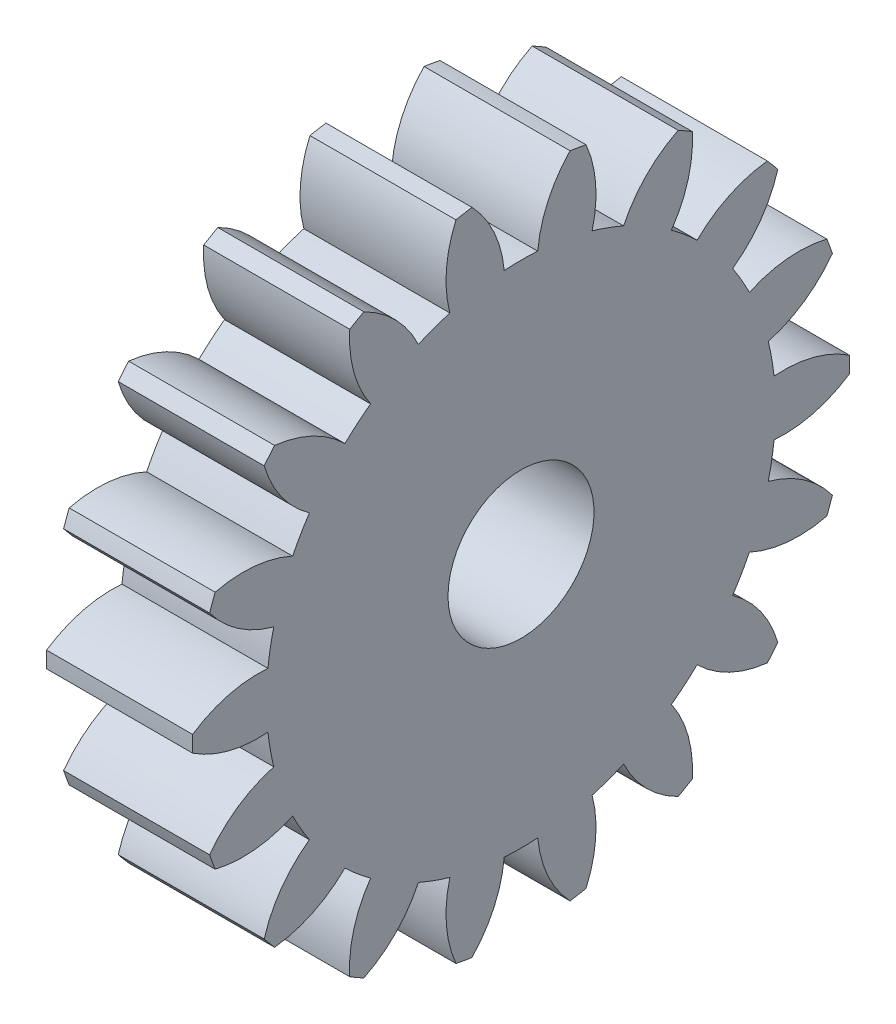
SolidWorks part; units mm, degrees
ref_plane "Plane1" through (0, 0, 0) normal (0, 0, 1) x (1, 0, 0)
ref_plane "Plane2" through (0, 0, 0) normal (0, 1, 0) x (1, 0, 0)
ref_plane "Plane3" through (0, 0, 0) normal (1, 0, 0) x (0, 0, -1)
sketch "HoldingSke" plane through (0, 0, 0) normal (0, 1, 0) x (1, 0, 0)
  line L0 (0, 0) -> (0.8454, -0.2747)
  line L1 (-15, 0) -> (100, 0) construction
  line L2 (0, 0) -> (-2.1039, 2.3779)
  line L3 (0, 0) -> (-11.863, 4.5341)
  line L4 (0, 0) -> (8.2133, 2.6687)
  line L5 (0, 0) -> (-46.8476, -17.4728)
  line L6 (0, 0) -> (-4.1448, -2.7965)
  line L7 (-2.1039, 2.3779) -> (8.6586, 51.2059)
  line L8 (-76.2, 54.61) -> (-75.3, 54.61)
  line L9 (-71.009, 38.7566) -> (-53.1078, 45.2721)
  line L10 (-76.2, 71.12) -> (104.1128, 71.12)
  line L11 (0, 0) -> (-5, 0)
  line L12 (-76.2, 101.6) -> (-76.158, 101.6)
  line L13 (24.9733, 27.94) -> (52.9518, 28.4284)
  line L14 (24.9733, 27.94) -> (24.9743, 27.94)
  line L15 (24.9733, 27.94) -> (100.4006, 29.5858)
  line L16 (-63.627, -1.125) -> (-12.827, -1.125)
  circle A0 centre (0, 0) radius 2.5
  circle A1 centre (0, 0) radius 8.7177
  circle A2 centre (0, 0) radius 37.5
  circle A3 centre (0, 0) radius 2.5
  dimension "Num_teeth" = 18
  dimension "Pitch_radius" = 180.3128
  dimension "Width" = 5
  dimension "Thickness" = 5
sketch "BasProSke" plane through (0, 0, 0) normal (0, 1, 0) x (1, 0, 0)
  line L0 (-10, 0) -> (60, 0) construction
  line L1 (0, 0) -> (0, 11.25)
  line L2 (0, 0) -> (5, 0)
  line L3 (5, 0) -> (5, 11.25)
  line L4 (5, 11.25) -> (0, 11.25)
  dimension "Thickness" = 5
  dimension "Diameter" = 22.5
revolve "Base-Revolve" add sketch "BasProSke" angle 360 about L0
sketch "TooCutSke" plane through (0, 0, 0) normal (1, 0, 0) x (0, 0, -1)
  line L1 (0, 0) -> (0, 107) construction
  line L2 (0, 0) -> (-0.9559, 10.0798) construction
  line L3 (0, 0) -> (-3.5051, 19.8786) construction
  line L4 (-0.9559, 10.0798) -> (-1.7526, 9.9393) construction
  arc A0 (0.5734, 8.6989) -> (-0.5734, 8.6989) centre (0, 0) ccw
  arc A1 (1.7004, 11.1464) -> (-1.7004, 11.1464) centre (0, 0) ccw
  circle A2 centre (0, 0) radius 10.125 construction
  circle A3 centre (0, 0) radius 9.5144 construction
  arc A4 (-0.5734, 8.6989) -> (-1.7004, 11.1464) centre (-4.6061, 8.3251) ccw
  arc A5 (1.7004, 11.1464) -> (0.5734, 8.6989) centre (4.6061, 8.3251) ccw
extrude "ToothCut" cut sketch "TooCutSke" along normal through all
fillet "Breaks" [suppressed] radius 0.0225 tangent propagation no
fillet "RootFillets" [suppressed] radius 0.2823
pattern_circular "TeethCuts" count 18 every 20 about axis through (-10, 0, 0) along (1, 0, 0) of "ToothCut", "RootFillets", "Breaks"
sketch "HubNeaOneSke" plane through (0, 0, 0) normal (-1, 0, 0) x (0, 0, 1)
  circle A0 centre (0, 0) radius 8.7177
  dimension "Diameter" = 17.4355
extrude "HubNearOne" [suppressed] add sketch "HubNeaOneSke" along normal blind 45.0001
sketch "HubNeaBotSke" plane through (0, 0, 0) normal (-1, 0, 0) x (0, 0, 1)
  circle A0 centre (0, 0) radius 8.7177
  dimension "Diameter" = 17.4355
extrude "HubNearBoth" [suppressed] add sketch "HubNeaBotSke" along normal blind 22.5
ref_plane "FarPln" through (5, 0, 0) normal (1, 0, 0) x (0, 0, -1)
sketch "HubFarSke" plane through (5, 0, 0) normal (1, 0, 0) x (0, 0, -1)
  circle A0 centre (0, 0) radius 8.7177
  dimension "Diameter" = 17.4355
extrude "HubFar" [suppressed] add sketch "HubFarSke" along normal blind 22.5
sketch "BorSke" plane through (0, 0, 0) normal (1, 0, 0) x (0, 0, -1)
  circle A0 centre (0, 0) radius 2.5
  dimension "Diameter" = 5
extrude "Bore" cut sketch "BorSke" along normal mid plane 100.0001
sketch "KeySke" plane through (0, 0, 0) normal (1, 0, 0) x (0, 0, -1)
  line L0 (-1, 0) -> (-1, 3.4)
  line L1 (-1, 3.4) -> (1, 3.4)
  line L2 (1, 3.4) -> (1, 0)
  line L3 (0, 0) -> (0, 34) construction
  line L4 (-1, 0) -> (1, 0)
  dimension "Width" = 2
extrude "Keyway" [suppressed] cut sketch "KeySke" along normal mid plane 100.0001
pattern_circular "Keyway2" [suppressed] count 2 every 90 about axis through (-10, 0, 0) along (1, 0, 0) reverse direction yes
equation "' \"Module@HoldingSke\" = 6.35"
equation "' \"Num_teeth@HoldingSke\" = 12"
equation "' \"Ap@HoldingSke\" =  20"
equation "' \"Ap@HoldingSke\" = 20"
equation "' \"Width@HoldingSke\" = 0.5 * 25.4"
equation "' \"Hub_dia@HoldingSke\"= 1 * 25.4"
equation "' \"Hub_dia@HoldingSke\" = 1 * 25.4"
equation "' \"Overall_len@HoldingSke\" = 1.0 * 25.4"
equation "' \"Bore@HoldingSke\" = 0.75 * 25.4"
equation "' \"T_dim@HoldingSke\" = 0.1 * 25.4"
equation "' \"Width@KeySke\" = 0.25 * 25.4"
equation "' \"Show_teeth@HoldingSke\" = 13"
equation "' \"Backlash@HoldingSke\" = 0.009 * 25.4"
equation "' \"Addendum_fac@HoldingSke\" = 1.0"
equation "' \"Dedendum_fac@HoldingSke\" = 1.25"
equation "' \"Dedendum_add@HoldingSke\" = 0.00005 * 25.4"
equation "' \"Clearance_fac@HoldingSke\" = 0.25"
equation "\"Pitch@HoldingSke\" = 1 / \"Module@HoldingSke\""
equation "\"Overcut_dia@TooCutSke\" = (\"Num_teeth@HoldingSke\" + 2 * \"Addendum_fac@HoldingSke\") / \"Pitch@HoldingSke\" + 0.002 * 25.4"
equation "\"Pitch_dia@TooCutSke\" = \"Num_teeth@HoldingSke\" / \"Pitch@HoldingSke\""
equation "\"Base_dia@TooCutSke\" = \"Num_teeth@HoldingSke\" / \"Pitch@HoldingSke\" * cos((\"Ap@HoldingSke\"  * 3.14159265 / 180))"
equation "\"Root_dia@TooCutSke\" = (\"Num_teeth@HoldingSke\" + 2) / \"Pitch@HoldingSke\" - 2 * (\"Addendum_fac@HoldingSke\" + \"Dedendum_fac@HoldingSke\") / \"Pitch@HoldingSke\" - \"Dedendum_add@HoldingSke\" * 2"
equation "\"Half_ang@TooCutSke\" = 180 / \"Num_teeth@HoldingSke\""
equation "\"Half_CT@TooCutSke\" = \"Num_teeth@HoldingSke\" / \"Pitch@HoldingSke\" * sin((3.14159265 / 2 / \"Num_teeth@HoldingSke\")) / 2 - 7 * \"Backlash@HoldingSke\" / 4"
equation "\"Flank_rad@TooCutSke\" = \"Num_teeth@HoldingSke\" / \"Pitch@HoldingSke\" / 5"
equation "\"Radius@RootFillets\" = \"Clearance_fac@HoldingSke\" / \"Pitch@HoldingSke\" + \"Dedendum_add@HoldingSke\""
equation "\"Break_rad@Breaks\" = 0.02 / \"Pitch@HoldingSke\""
equation "\"Thickness@HoldingSke\" = \"Width@HoldingSke\""
equation "\"OAL@HoldingSke\" = \"Thickness@HoldingSke\""
equation "\"MHD@HoldingSke\" = (\"Num_teeth@HoldingSke\" + 2) / \"Pitch@HoldingSke\" - 2 * (\"Addendum_fac@HoldingSke\" + \"Dedendum_fac@HoldingSke\")  / \"Pitch@HoldingSke\" - \"Dedendum_add@HoldingSke\" * 2"
equation "\"MBD@HoldingSke\" = (\"Num_teeth@HoldingSke\" + 2) / \"Pitch@HoldingSke\" - 2 * (\"Addendum_fac@HoldingSke\" + \"Dedendum_fac@HoldingSke\")  / \"Pitch@HoldingSke\" - \"Dedendum_add@HoldingSke\" * 2 - 0.002 * 25.4"
equation "\"MHD@HoldingSke\" = ((sgn( \"MHD@HoldingSke\" - \"Hub_dia@HoldingSke\" )-1)*( \"MHD@HoldingSke\" - \"Hub_dia@HoldingSke\" ))/-2+ \"Hub_dia@HoldingSke\""
equation "\"MBD@HoldingSke\" = ((sgn( \"MBD@HoldingSke\" - \"Bore@HoldingSke\" )-1)*( \"MBD@HoldingSke\" - \"Bore@HoldingSke\" ))/-2+ \"Bore@HoldingSke\""
equation "\"OAL@HoldingSke\" = ((sgn( \"OAL@HoldingSke\" - \"Overall_len@HoldingSke\" )+1)*( \"OAL@HoldingSke\" - \"Overall_len@HoldingSke\" ))/2 + \"Overall_len@HoldingSke\" + 0.000002 * 25.4"
equation "\"Num_teeth@TeethCuts\" = int( \"Show_teeth@HoldingSke\" ) + 1"
equation "\"Num_teeth@TeethCuts\" = ((sgn( \"Num_teeth@TeethCuts\" - \"Num_teeth@HoldingSke\" )-1)*( \"Num_teeth@TeethCuts\" - \"Num_teeth@HoldingSke\" ))/-2+ \"Num_teeth@HoldingSke\""
equation "\"Num_teeth@TeethCuts\" = ((sgn( \"Num_teeth@TeethCuts\" - 2.0)+1)*( \"Num_teeth@TeethCuts\" - 2.0))/2 +2.0"
equation "\"Angle@TeethCuts\" = 360.0 / \"Num_teeth@HoldingSke\""
equation "\"Diameter@BasProSke\" = (\"Num_teeth@HoldingSke\" + 2 * \"Addendum_fac@HoldingSke\") / \"Pitch@HoldingSke\""
equation "\"Thickness@BasProSke\"  = \"Thickness@HoldingSke\""
equation "' \"Fillet_rad@BasProSke\" =  \"Thickness@HoldingSke\" * 0.05"
equation "' \"Fillet_rad@BasProSke\" = \"Thickness@HoldingSke\" * 0.05"
equation "\"MHD@HoldingSke\" = ((sgn( \"MHD@HoldingSke\" - \"Root_dia@TooCutSke\" )-1)*( \"MHD@HoldingSke\" - \"Root_dia@TooCutSke\" ))/-2+ \"Root_dia@TooCutSke\""
equation "\"Diameter@HubNeaOneSke\" = \"MHD@HoldingSke\""
equation "\"Length@HubNearOne\" = \"OAL@HoldingSke\" - \"Thickness@BasProSke\""
equation "\"Diameter@HubNeaBotSke\" = \"MHD@HoldingSke\""
equation "\"Length@HubNearBoth\" = ( \"OAL@HoldingSke\" - \"Thickness@BasProSke\" ) / 2.0"
equation "\"Thickness@FarPln\" = \"Thickness@BasProSke\""
equation "\"Diameter@HubFarSke\" = \"MHD@HoldingSke\""
equation "\"Length@HubFar\" = ( \"OAL@HoldingSke\" - \"Thickness@BasProSke\" ) / 2.0"
equation "\"Diameter@BorSke\" = \"MBD@HoldingSke\""
equation "\"D1@Bore\" = \"OAL@HoldingSke\" * 2.0"
equation "\"D1@Keyway\" = \"OAL@HoldingSke\" * 2.0"
equation "\"Offset@KeySke\" = \"T_dim@HoldingSke\" + \"MBD@HoldingSke\" / 2.0"
